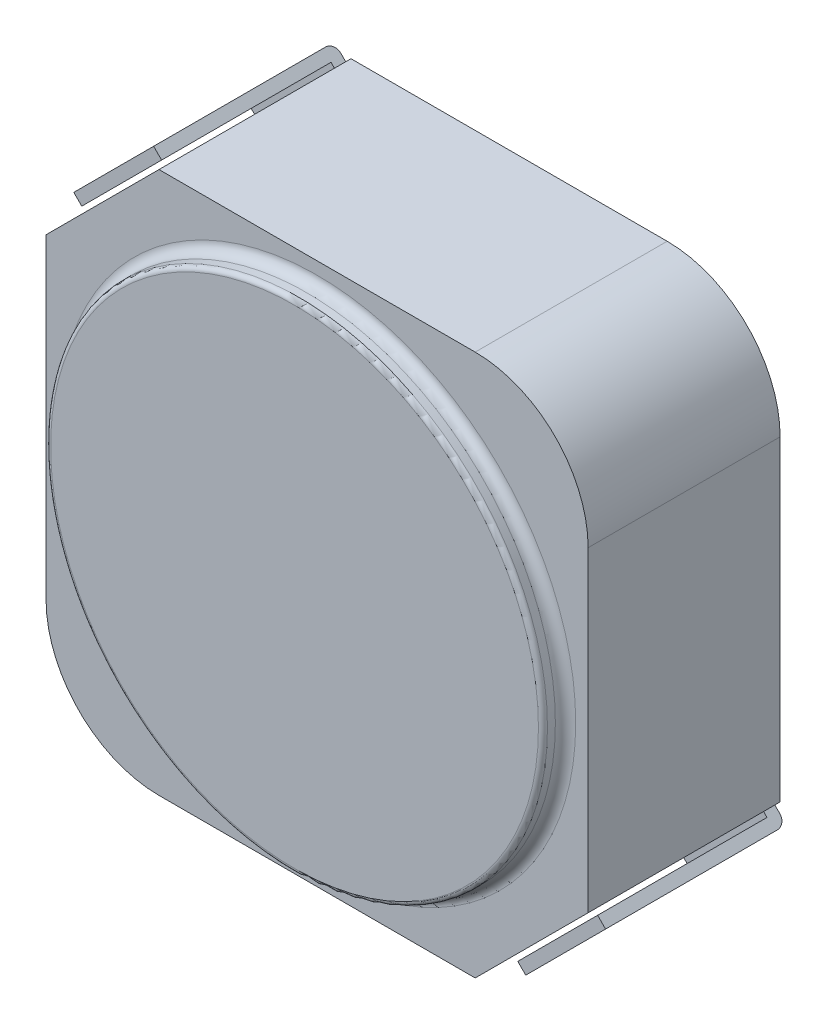
SolidWorks part; units mm, degrees
ref_plane "Спереди" through (0, 0, 0) normal (0, 0, 1) x (1, 0, 0)
ref_plane "Сверху" through (0, 0, 0) normal (0, 1, 0) x (1, 0, 0)
ref_plane "Справа" through (0, 0, 0) normal (1, 0, 0) x (0, 0, -1)
sketch "Эскиз2" plane through (0, 0, 0) normal (0, 0, 1) x (1, 0, 0)
  line L1 (-1.4, 2.4) -> (1.4, 2.4)
  line L2 (-2.4, 1.4) -> (-2.4, -1.4)
  line L3 (-1.4, -2.4) -> (1.4, -2.4)
  line L4 (2.4, 1.4) -> (2.4, -1.4)
  line L6 (-2.4, 1.4) -> (-1.4, 2.4)
  line L9 (1.4, -2.4) -> (2.4, -1.4)
  arc A0 (-2.4, -1.4) -> (-1.4, -2.4) centre (-1.4, -1.4) ccw
  arc A1 (2.4, 1.4) -> (1.4, 2.4) centre (1.4, 1.4) ccw
  point P0 (-2.4, 2.4)
  point P1 (2.4, -2.4)
  dimension "D1" = 1
  dimension "D2" = 1
extrude "Вытянуть1" add sketch "Эскиз2" along normal blind 1.7 from offset 0.1
sketch "Эскиз6" plane through (0, 0, 0) normal (0, 0, 1) x (1, 0, 0)
  circle A1 centre (0, 0) radius 2
extrude "Вытянуть5" cut sketch "Эскиз6" along normal blind 0.3
sketch "Эскиз8" plane through (0, 0, 0) normal (0, 0, 1) x (1, 0, 0)
  circle A0 centre (0, 0) radius 1.7
extrude "Вытянуть9" add sketch "Эскиз8" along normal blind 0.25 from offset 0.1
sketch "Эскиз9" plane through (0, 0, 0) normal (0, 0, 1) x (1, 0, 0)
  circle A0 centre (0, 0) radius 2.2
extrude "Бобышка-Вытянуть1" add sketch "Эскиз9" along normal blind 0.5 from offset 1.5
fillet "Скругление2" radius 0.09 1 edges at (2.2, 0, 1.8)
fillet "Скругление3" radius 0.04 1 edges at (2.2, 0, 2)
sketch "Эскиз10" plane through (0, 0, 0) normal (0, 0, 1) x (1, 0, 0)
  line L0 (2.25, 0.75) -> (1.5, 0.75)
  line L1 (-2.25, 0.75) -> (-1.5, 0.75)
  line L2 (1.5, 2.25) -> (-1.55, 2.25)
  line L3 (2.25, 0.75) -> (2.25, 1.5)
  line L4 (-2.25, 0.75) -> (-2.25, 1.55)
  line L5 (1.5, 2.25) -> (2.25, 1.5)
  line L6 (-1.55, 2.25) -> (-2.25, 1.55)
  line L7 (-2.25, -0.75) -> (-1.5, -0.75)
  line L8 (2.25, -0.75) -> (1.5, -0.75)
  line L9 (-1.5, -2.25) -> (1.55, -2.25)
  line L10 (-2.25, -0.75) -> (-2.25, -1.5)
  line L11 (2.25, -0.75) -> (2.25, -1.55)
  line L12 (-1.5, -2.25) -> (-2.25, -1.5)
  line L13 (1.55, -2.25) -> (2.25, -1.55)
  arc A0 (1.5, 0.75) -> (-1.5, 0.75) centre (0, 0) ccw
  arc A1 (-1.5, -0.75) -> (1.5, -0.75) centre (0, 0) ccw
  dimension "D1" = 2
extrude "Бобышка-Вытянуть2" add sketch "Эскиз10" along normal blind 0.1
ref_axis "Ось1" through (0, 0, -0.15) along (0, 0, 1)
ref_plane "Плоскость2" through (0, 0, 0) normal (-0.7071, 0.7071, 0) x (-0.7071, -0.7071, 0)
sketch "Эскиз11" plane through (0, 0, 0) normal (0.7071, -0.7071, 0) x (0, 0, -1)
  line L1 (-1.6, 0.5) -> (-0.1, 0.5)
  line L2 (-1.6, 0.5) -> (-1.6, -0.5)
  line L3 (-1.6, -0.5) -> (-0.1, -0.5)
  line L4 (-0.1, 0.5) -> (-0.1, -0.5)
extrude "Бобышка-Вытянуть3" add sketch "Эскиз11" along normal blind 0.1 from offset 2.73 separate body
extrude "Бобышка-Вытянуть4" add sketch "Эскиз11<2>" against normal blind 0.1 from offset 2.73 separate body offset against normal yes
sketch "Эскиз11<2>" plane through (0, 0, 0) normal (0.7071, -0.7071, 0) x (0, 0, -1) same geometry as "Эскиз11"
ref_plane "Плоскость3" through (0, 0, 0) normal (-0.7071, -0.7071, 0) x (0.7071, -0.7071, 0)
sketch "Эскиз12" plane through (0, 0, 0) normal (-0.7071, -0.7071, 0) x (0.7071, -0.7071, 0)
  line L0 (2.83, 0.15) -> (2.83, 0.08)
  line L1 (2.75, 0) -> (2.6, 0)
  line L2 (2.6, 0.1) -> (2.73, 0.1)
  line L3 (2.73, 0.1) -> (2.73, 0.15)
  line L4 (2.73, 0.15) -> (2.83, 0.15)
  line L5 (2.6, 0.1) -> (2.6, 0)
  line L6 (0, -0.6039) -> (0, -0.4596) construction
  line L7 (-2.6, 0.1) -> (-2.6, 0)
  line L8 (-2.73, 0.15) -> (-2.83, 0.15)
  line L9 (-2.73, 0.1) -> (-2.73, 0.15)
  line L10 (-2.6, 0.1) -> (-2.73, 0.1)
  line L11 (-2.75, 0) -> (-2.6, 0)
  line L12 (-2.83, 0.15) -> (-2.83, 0.08)
  arc A0 (2.83, 0.08) -> (2.75, 0) centre (2.75, 0.08) cw
  arc A1 (-2.83, 0.08) -> (-2.75, 0) centre (-2.75, 0.08) ccw
  dimension "D1" = 0.08
extrude "Бобышка-Вытянуть5" add sketch "Эскиз12" against normal blind 1 from offset 0.5
